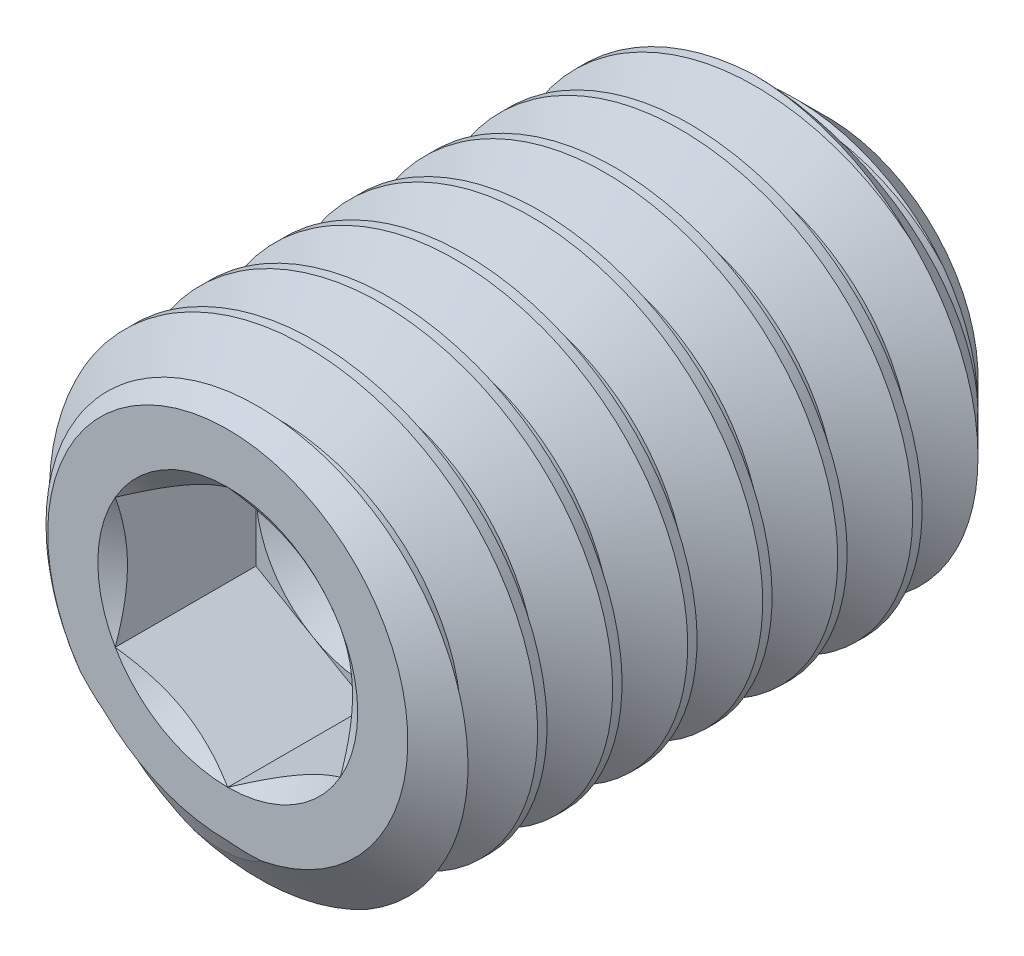
SolidWorks part; units mm, degrees
ref_plane "Front" through (0, 0, 0) normal (0, 0, 1) x (1, 0, 0)
ref_plane "Top" through (0, 0, 0) normal (0, 1, 0) x (1, 0, 0)
ref_plane "Right" through (0, 0, 0) normal (1, 0, 0) x (0, 0, -1)
sketch "Sketch22" plane through (0, 0, 0) normal (1, 0, 0) x (0, 0, -1)
  line L0 (-2, 0) -> (-2, 1.2)
  line L1 (-2, 1.2) -> (-1.7899, 1.5)
  line L2 (-1.7899, 1.5) -> (1.5, 1.5)
  line L3 (1.5, 1.5) -> (2, 1)
  line L4 (-0.145, 1.5) -> (-0.145, -1.5) construction
  line L5 (2, 0) -> (-2, 0)
  line L6 (-2, 1.2) -> (-2, -1.2) construction
  line L7 (2, 0) -> (2, 1)
  point P11 (-0.145, 0)
  dimension "D1" = 2.4
  dimension "Dia" = 3
  dimension "D2" = 0.5
  dimension "Length" = 4
  dimension "D3" = 35
  dimension "D6" = 45
revolve "Revolve1" add sketch "Sketch22" angle 360 about L5
ref_plane "Plane1" through (0, 0, -2) normal (0, 0, 1) x (1, 0, 0)
sketch "Sketch27" plane through (0, 0, -2) normal (0, 0, 1) x (1, 0, 0)
  circle A0 centre (0, 0) radius 1.5 construction
  circle A1 centre (0, 0) radius 1.5
curve "Helix/Spiral1" pitch 0.5 height 4.5 radius 1.5 centre (0, 0, -2) axis (0, 0, 1) start towards (0, 1, 0)
sketch "Sketch28" plane through (0, 0, 0) normal (1, 0, 0) x (0, 0, -1)
  line L0 (2, 1.5) -> (2.4375, 1.5)
  line L1 (2.4375, 1.5) -> (2.25, 1.1752)
  line L2 (2.25, 1.1752) -> (2.1875, 1.1752)
  line L3 (2.1875, 1.1752) -> (2, 1.5)
  line L4 (2.0937, 1.3376) -> (2.3437, 1.3376) construction
  line L6 (-1.7899, 1.5) -> (1.5, 1.5) construction
  dimension "D1" = 0.0625
  dimension "D2" = 0.25
  dimension "D3" = 60
sweep "Cut-Sweep2" cut profiles "Sketch28" path "Helix/Spiral1"
sketch "Sketch23" plane through (0, 0, 2) normal (0, 0, 1) x (1, 0, 0)
  line L1 (0, 0.866) -> (-0.75, 0.433)
  line L2 (-0.75, 0.433) -> (-0.75, -0.433)
  line L3 (-0.75, -0.433) -> (0, -0.866)
  line L4 (0, -0.866) -> (0.75, -0.433)
  line L5 (0.75, -0.433) -> (0.75, 0.433)
  line L6 (0.75, 0.433) -> (0, 0.866)
  circle A0 centre (0, 0) radius 0.75 construction
  dimension "Hex" = 1.5
extrude "Cut-Extrude10" cut sketch "Sketch23" against normal blind 0.9375
sketch "Sketch24" plane through (0, 0, 2) normal (0, 0, 1) x (1, 0, 0)
  circle A0 centre (0, 0) radius 0.866
extrude "Cut-Extrude11" cut sketch "Sketch24" against normal through all draft 55
sketch "Sketch26" plane through (0, 0, 1.0625) normal (0, 0, 1) x (1, 0, 0)
  circle A0 centre (0, 0) radius 0.75 construction
  circle A1 centre (0, 0) radius 0.75
extrude "Cut-Extrude12" cut sketch "Sketch26" against normal through all draft 60
sketch "Sketch30" plane through (0, 0, 0) normal (1, 0, 0) x (0, 0, -1)
  line L0 (-1.7899, 1.5) -> (1.5, 1.5) construction
  line L1 (-2, 0) -> (-2, 1.2) construction
  line L2 (2, 0) -> (2, 1) construction
  point P0 (-2, 1.5)
  point P1 (2, 1.5)
  point P2 (2, -1.5)
  point P11 (0.75, -1.5)
  dimension "D1" = 1.25
equation "\"D1@Sketch28\" = \"D4@Helix/Spiral1\" * .125"
equation "\"D2@Sketch28\" = \"D4@Helix/Spiral1\" * .5"
equation "\"D3@Helix/Spiral1\" = \"Length@Sketch22\" + \"D4@Helix/Spiral1\""
equation "\"D1@Sketch30\" = \"D4@Helix/Spiral1\" * 2.5"
equation "\"hex Depth@Cut-Extrude10\" = \"Hex@Sketch23\" * .625"
equation "\"D1@Sketch22\" = \"Dia@Sketch22\" * .8"
equation "\"D2@Sketch22\" = \"D4@Helix/Spiral1\""
